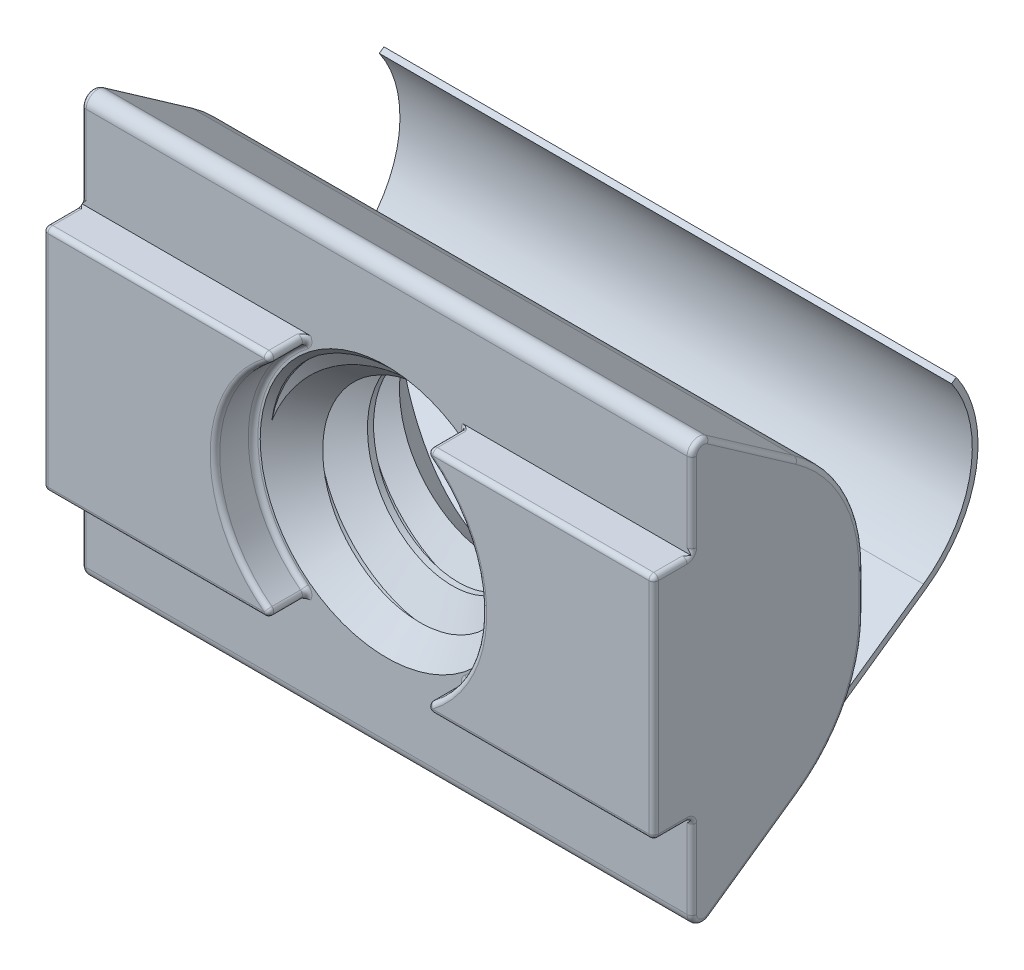
SolidWorks part; units mm, degrees
ref_plane "Front Plane" through (0, 0, 0) normal (0, 0, 1) x (1, 0, 0)
ref_plane "Top Plane" through (0, 0, 0) normal (0, 1, 0) x (1, 0, 0)
ref_plane "Right Plane" through (0, 0, 0) normal (1, 0, 0) x (0, 0, -1)
sketch "Sketch1" plane through (0, 0, 0) normal (0, 0, 1) x (1, 0, 0)
  line L1 (-8, 5.5) -> (8, 5.5)
  line L2 (-8, 5.5) -> (-8, -5.5)
  line L3 (-8, -5.5) -> (8, -5.5)
  line L4 (8, 5.5) -> (8, -5.5)
  circle A0 centre (0, 0) radius 3.175
  circle A1 centre (0, 0) radius 3.5
  point P4 (0, 5.5)
  point P5 (0, 0)
  point P6 (-8, 0)
  point P11 (0, 3.175)
  dimension "Thread Diameter" = 6.35
  dimension "Counterbore Diameter" = 7
  dimension "Length" = 16
  dimension "Width" = 11
sketch "Sketch2" plane through (0, 0, 0) normal (1, 0, 0) x (0, 0, -1)
  line L0 (-2.75, -3) -> (-2.75, 3)
  line L1 (-2.75, 3) -> (-1.75, 3)
  line L2 (-1.75, 3) -> (-1.75, 5.2)
  line L3 (-1.2779, 5.4457) -> (1.0443, 3.8197)
  line L4 (-2.75, -3) -> (-1.75, -3)
  line L5 (-1.75, -3) -> (-1.75, -5.2)
  line L6 (-1.2779, -5.4457) -> (1.0443, -3.8197)
  line L7 (2.75, 0.5431) -> (2.75, -0.5431)
  line L8 (-2.75, 0) -> (2.75, 0)
  line L9 (4.9068, -1.2983) -> (-1.164, -5.5491)
  line L10 (-1.164, -5.5491) -> (-1.25, -5.4262)
  line L11 (-1.25, -5.4262) -> (4.8207, -1.1754)
  line L12 (5.5575, 3.0028) -> (5.6803, 3.0888)
  line L13 (-3.9406, 3.3125) -> (-3.3056, 2.2126)
  line L14 (-3.3056, 2.2126) -> (-2.6706, 3.3125)
  line L15 (-2.6706, 3.3125) -> (-3.9406, 3.3125)
  line L16 (-3.3056, 3.3125) -> (-3.3056, 3.175)
  line L17 (-3.3056, 2.2126) -> (-3.3056, 2.3501)
  line L18 (-3.8613, 3.175) -> (-2.75, 3.175)
  line L19 (-3.9009, 3.2437) -> (-2.7103, 3.2437)
  line L20 (-3.385, 2.3501) -> (-3.2263, 2.3501)
  arc A0 (1.0443, -3.8197) -> (2.75, -0.5431) centre (-1.25, -0.5431) ccw
  arc A1 (2.75, 0.5431) -> (1.0443, 3.8197) centre (-1.25, 0.5431) ccw
  arc A2 (-1.2779, -5.4457) -> (-1.75, -5.2) centre (-1.45, -5.2) cw
  arc A3 (-1.75, 5.2) -> (-1.2779, 5.4457) centre (-1.45, 5.2) cw
  arc A4 (4.8207, -1.1754) -> (5.5575, 3.0028) centre (3.1, 1.282) ccw
  arc A5 (4.9068, -1.2983) -> (5.6803, 3.0888) centre (3.1, 1.282) ccw
  point P12 (0, 0)
  point P22 (-1.45, 5.5)
  point P30 (6.25, 1.282)
  point P39 (-3.3056, 3.175)
  point P42 (-3.3056, 3.2437)
  point P45 (-3.3056, 2.3501)
  dimension "D4" = 4
  dimension "D10" = 3
  dimension "Thickness" = 5.5
  dimension "D2" = 6
  dimension "D6" = 35
  dimension "Spring Thickness" = 0.15
  dimension "D8" = 0.5
  dimension "Spring Length" = 8
  dimension "D11" = 35
  dimension "Thread Pitch" = 1.27
  dimension "D12" = 0.1588
sketch "Sketch3" plane through (0, 0, 0) normal (0, 1, 0) x (1, 0, 0)
  line L0 (-7.5, -1.25) -> (-7.5, 10.09)
  line L1 (-6.5, 11.09) -> (-5.25, 11.09)
  line L2 (-4.25, 10.09) -> (-4.25, 5.05)
  line L4 (4.25, 5.05) -> (4.25, 10.09)
  line L5 (5.25, 11.09) -> (6.5, 11.09)
  line L6 (7.5, 10.09) -> (7.5, -1.25)
  line L7 (7.5, -1.25) -> (-7.5, -1.25)
  arc A1 (-4.25, 5.05) -> (4.25, 5.05) centre (0, 5.05) ccw
  arc A2 (7.5, 10.09) -> (6.5, 11.09) centre (6.5, 10.09) ccw
  arc A3 (5.25, 11.09) -> (4.25, 10.09) centre (5.25, 10.09) ccw
  arc A4 (-4.25, 10.09) -> (-5.25, 11.09) centre (-5.25, 10.09) ccw
  arc A5 (-6.5, 11.09) -> (-7.5, 10.09) centre (-6.5, 10.09) ccw
  point P19 (-7.5, 11.09)
  dimension "D2" = 4.25
  dimension "Spring Width" = 15
  dimension "D3" = 6.3
  dimension "Flat Spring Length" = 12.34
  dimension "D5" = 8.5
sketch "Sketch4" plane through (0, 0, 0) normal (1, 0, 0) x (0, 0, -1)
  line L0 (-1.2779, -5.4457) -> (1.0443, -3.8197) construction
  line L1 (2.75, 0.5431) -> (2.75, -0.5431) construction
  line L2 (-1.75, -3) -> (-1.75, -5.2) construction
  line L3 (-2.75, -3) -> (-1.75, -3) construction
  line L4 (-2.75, -3) -> (-2.75, 3) construction
  line L5 (-2.75, 3) -> (-1.75, 3) construction
  line L6 (-1.75, 3) -> (-1.75, 5.2) construction
  line L7 (-1.2779, 5.4457) -> (1.0443, 3.8197) construction
  line L8 (-1.2779, -5.4457) -> (1.0443, -3.8197)
  line L9 (2.75, 0.5431) -> (2.75, -0.5431)
  line L10 (-1.75, -3) -> (-1.75, -5.2)
  line L11 (-2.75, -3) -> (-1.75, -3)
  line L12 (-2.75, -3) -> (-2.75, 3)
  line L13 (-2.75, 3) -> (-1.75, 3)
  line L14 (-1.75, 3) -> (-1.75, 5.2)
  line L15 (-1.2779, 5.4457) -> (1.0443, 3.8197)
  arc A0 (1.0443, -3.8197) -> (2.75, -0.5431) centre (-1.25, -0.5431) ccw construction
  arc A1 (-1.75, -5.2) -> (-1.2779, -5.4457) centre (-1.45, -5.2) ccw construction
  arc A2 (-1.2779, 5.4457) -> (-1.75, 5.2) centre (-1.45, 5.2) ccw construction
  arc A3 (2.75, 0.5431) -> (1.0443, 3.8197) centre (-1.25, 0.5431) ccw construction
  arc A4 (1.0443, -3.8197) -> (2.75, -0.5431) centre (-1.25, -0.5431) ccw
  arc A5 (-1.75, -5.2) -> (-1.2779, -5.4457) centre (-1.45, -5.2) ccw
  arc A6 (-1.2779, 5.4457) -> (-1.75, 5.2) centre (-1.45, 5.2) ccw
  arc A7 (2.75, 0.5431) -> (1.0443, 3.8197) centre (-1.25, 0.5431) ccw
extrude "Boss-Extrude1" add sketch "Sketch4" against normal up to vertex (8 mm away) and the other way up to vertex (8 mm away) up to point (-8, 5.5, 0) other way up to point (8, 5.5, 0)
sketch "Sketch5" plane through (0, 0, 2.75) normal (0, 0, 1) x (1, 0, 0)
  circle A0 centre (0, 0) radius 3.5 construction
  circle A1 centre (0, 0) radius 3.5
extrude "Cut-Extrude1" cut sketch "Sketch5" against normal up to surface (1 mm away) up to face at (0, 4.1, 1.75)
sketch "Sketch6" plane through (0, 0, 2.75) normal (0, 0, 1) x (1, 0, 0)
  circle A0 centre (0, 0) radius 3.175 construction
  circle A1 centre (0, 0) radius 3.175
extrude "Cut-Extrude2" cut sketch "Sketch6" against normal through all
sketch "Sketch7" plane through (0, 0, 0) normal (1, 0, 0) x (0, 0, -1)
  line L0 (-1.164, -5.5491) -> (-1.25, -5.4262) construction
  line L1 (-1.25, -5.4262) -> (4.8207, -1.1754) construction
  line L2 (4.9068, -1.2983) -> (-1.164, -5.5491) construction
  line L3 (5.5575, 3.0028) -> (5.6803, 3.0888) construction
  line L4 (-1.164, -5.5491) -> (-1.25, -5.4262)
  line L5 (-1.25, -5.4262) -> (4.8207, -1.1754)
  line L6 (4.9068, -1.2983) -> (-1.164, -5.5491)
  line L7 (5.5575, 3.0028) -> (5.6803, 3.0888)
  arc A0 (4.9068, -1.2983) -> (5.6803, 3.0888) centre (3.1, 1.282) ccw construction
  arc A1 (4.8207, -1.1754) -> (5.5575, 3.0028) centre (3.1, 1.282) ccw construction
  arc A2 (4.9068, -1.2983) -> (5.6803, 3.0888) centre (3.1, 1.282) ccw
  arc A3 (4.8207, -1.1754) -> (5.5575, 3.0028) centre (3.1, 1.282) ccw
extrude "Boss-Extrude2" add sketch "Sketch7" against normal up to vertex (7.5 mm away) and the other way up to vertex (7.5 mm away) separate body up to point (-7.5, 0, 1.25) other way up to point (7.5, 0, 1.25)
fillet "Fillet2" radius 0.125 4 edges at (-1.8028, -3, 2.25) (1.8028, -3, 2.25) (1.8028, 3, 2.25) (-1.8028, 3, 2.25)
fillet "Fillet3" radius 0.125 44 edges at (5.104, -3, 2.75) (2.0896, -2.9152, 2.75) (5.104, 3, 2.75) (2.0896, 2.9152, 2.75) (5.104, 3, 1.75) (2.0896, 2.9152, 1.75) (5.104, -3, 1.75) (2.0896, -2.9152, 1.75) (-5.104, -3, 2.75) (-2.0896, -2.9152, 2.75) (-3.5, 0, 2.75) (-2.0896, 2.9152, 2.75) (-5.104, -3, 1.75) (-2.0896, -2.9152, 1.75) (-5.104, 3, 1.75) (-2.0896, 2.9152, 1.75) (8, -4.1, 1.75) (8, -3, 2.25) (8, 0, 2.75) (8, 3, 2.25) (8, 4.1, 1.75) (8, 5.4661, 1.5885) (8, 4.6327, 0.1168) (8, 2.3901, -2.298) (8, 0, -2.75) (8, -2.3901, -2.298) (8, -4.6327, 0.1168) (8, -5.4661, 1.5885) (-8, -4.6327, 0.1168) (-8, -2.3901, -2.298) (-8, 0, -2.75) (-8, 2.3901, -2.298) (-8, 4.6327, 0.1168) (-8, 5.4661, 1.5885) (-8, 4.1, 1.75) (-8, 3, 2.25) (-8, 0, 2.75) (-8, -3, 2.25) (-8, -4.1, 1.75) (-8, -5.4661, 1.5885) (3.5, 0, 2.75) (3.5, 0, 1.75) (-5.104, 3, 2.75) (-3.5, 0, 1.75)
sketch "Sketch9" plane through (0, 0, 0) normal (0, 0, 1) x (1, 0, 0)
  line L0 (0, 0) -> (2.2451, -2.2451)
  line L1 (7.5, 0) -> (-7.5, 0) construction
  circle A0 centre (0, 0) radius 3.175 construction
  circle A1 centre (0, 0) radius 3.175
  point P0 (-8, 5.5)
  point P1 (8, 5.5)
  point P3 (-8, -5.5)
  point P13 (2.2451, -2.2451)
  dimension "D1" = 45
sketch "Sketch10" plane through (0, 0, 0) normal (1, 0, 0) x (0, 0, -1)
  point P0 (-2.75, 3)
  point P1 (2.75, 0.5431)
  point P3 (6.25, 1.282)
  point P5 (-2.75, -3)
sketch "Sketch11" plane through (0, 0, 2.75) normal (0, 0, 1) x (1, 0, 0)
  circle A0 centre (0, 0) radius 3.175
curve "Helix/Spiral1" pitch 1.27 height 6.77 radius 3.175 centre (0, 0, 2.75) axis (0, 0, -1) start towards (0, 1, 0)
sketch "Sketch12" plane through (0, 0, 0) normal (1, 0, 0) x (0, 0, -1)
  line L0 (-3.385, 2.3501) -> (-3.2263, 2.3501) construction
  line L1 (-3.9406, 3.3125) -> (-3.3056, 2.2126) construction
  line L2 (-3.3056, 2.2126) -> (-2.6706, 3.3125) construction
  line L3 (-3.9009, 3.2437) -> (-2.7103, 3.2437) construction
  line L4 (-3.385, 2.3501) -> (-3.2263, 2.3501)
  line L5 (-3.9009, 3.2437) -> (-3.385, 2.3501)
  line L6 (-3.2263, 2.3501) -> (-2.7103, 3.2437)
  line L7 (-3.9009, 3.2437) -> (-2.7103, 3.2437)
sweep "Sweep1" add profiles "Sketch12" path "Helix/Spiral1"
sketch "Sketch13" plane through (0, 0, 1.75) normal (0, 0, 1) x (1, 0, 0)
  circle A0 centre (0, 0) radius 3.3125
extrude "Cut-Extrude4" cut sketch "Sketch13" against normal through all draft 45 and the other way through all
sketch "Sketch14" plane through (8, 0, 0) normal (1, 0, 0) x (0, 0, -1)
  line L8 (-1.2779, -5.4457) -> (1.0443, -3.8197)
  line L9 (2.75, -0.5431) -> (2.75, 0.5431)
  line L10 (1.0443, 3.8197) -> (-1.2779, 5.4457)
  line L11 (-1.75, 5.2) -> (-1.75, 3)
  line L12 (-1.75, 3) -> (-2.75, 3)
  line L13 (-2.75, 3) -> (-2.75, -3)
  line L14 (-2.75, -3) -> (-1.75, -3)
  line L15 (-1.75, -3) -> (-1.75, -5.2)
  line L16 (-1.2779, -5.4457) -> (1.0443, -3.8197)
  line L17 (2.75, -0.5431) -> (2.75, 0.5431)
  line L18 (1.0443, 3.8197) -> (-1.2779, 5.4457)
  line L19 (-1.75, 5.2) -> (-1.75, 3)
  line L20 (-1.75, 3) -> (-2.75, 3)
  line L21 (-2.75, 3) -> (-2.75, -3)
  line L22 (-2.75, -3) -> (-1.75, -3)
  line L23 (-1.75, -3) -> (-1.75, -5.2)
  arc A4 (1.0443, -3.8197) -> (2.75, -0.5431) centre (-1.25, -0.5431) ccw
  arc A5 (2.75, 0.5431) -> (1.0443, 3.8197) centre (-1.25, 0.5431) ccw
  arc A6 (-1.2779, 5.4457) -> (-1.75, 5.2) centre (-1.45, 5.2) ccw
  arc A7 (-1.75, -5.2) -> (-1.2779, -5.4457) centre (-1.45, -5.2) ccw
  arc A8 (1.0443, -3.8197) -> (2.75, -0.5431) centre (-1.25, -0.5431) ccw
  arc A9 (2.75, 0.5431) -> (1.0443, 3.8197) centre (-1.25, 0.5431) ccw
  arc A10 (-1.2779, 5.4457) -> (-1.75, 5.2) centre (-1.45, 5.2) ccw
  arc A11 (-1.75, -5.2) -> (-1.2779, -5.4457) centre (-1.45, -5.2) ccw
  dimension "D1" = 0
extrude "Cut-Extrude5" cut sketch "Sketch14" against normal through all flip side to cut
sketch "Sketch16" plane through (0, 0, 0) normal (1, 0, 0) x (0, 0, -1)
  line L0 (2.75, 0) -> (2.75, 4.1628)
  line L1 (2.75, 3.175) -> (1.7622, 3.175) construction
  line L2 (2.75, 4.1628) -> (0, 1.4128)
  line L3 (0, 1.4128) -> (0, 0)
  line L4 (0, 0) -> (2.75, 0)
  line L5 (-3.8613, 3.175) -> (-2.75, 3.175) construction
  arc A0 (2.75, 0.5431) -> (1.0443, 3.8197) centre (-1.25, 0.5431) ccw construction
  point P5 (0, 0)
  point P9 (0, 0)
  dimension "D1" = 45
  dimension "D2" = 2.75
revolve "Cut-Revolve1" cut sketch "Sketch16" angle 360 about L4
equation "\"D12@Sketch2\"=\"Thread Pitch@Sketch2\"/8"
equation "\"D1@Sketch8\"=\"D3@Sketch3\""
equation "\"D1\" = \"D6@Sketch3\""
equation "\"D3@Helix/Spiral1\"=\"Thickness@Sketch2\"+\"Thread Pitch@Sketch2\""
equation "\"D4@Helix/Spiral1\"=\"Thread Pitch@Sketch2\""
equation "\"D1@Sketch17\"=\"Spring Width@Sketch3\"*.82"
equation "\"D2@Sketch17\"=\"Spring Width@Sketch3\"*.06"
equation "\"D1\" = \"Spring Thickness@Sketch2\" * .5"
